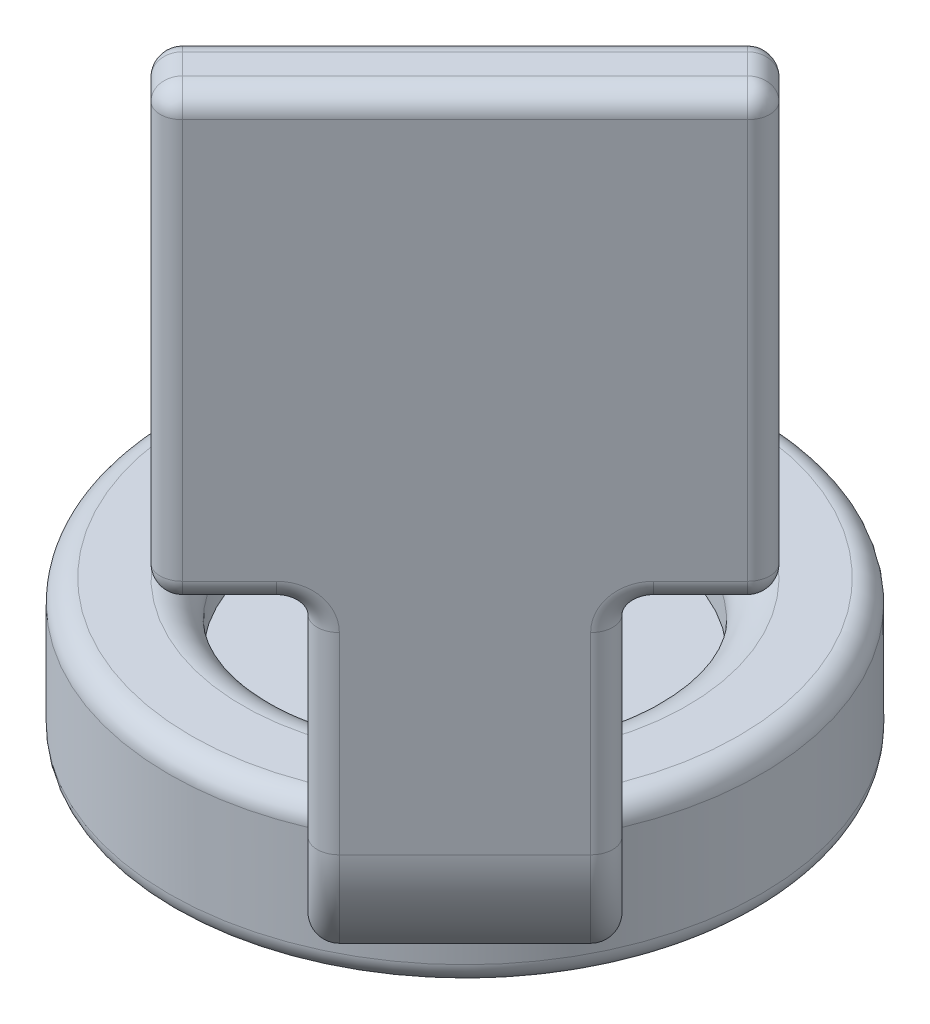
SolidWorks part; units mm, degrees
ref_plane "前视基准面" through (0, 0, 0) normal (0, 0, 1) x (1, 0, 0)
ref_plane "上视基准面" through (0, 0, 0) normal (0, 1, 0) x (1, 0, 0)
ref_plane "右视基准面" through (0, 0, 0) normal (1, 0, 0) x (0, 0, -1)
other "Configuration Table"
sketch "草图2" plane through (0, 0, 0) normal (0, 0, 1) x (1, 0, 0)
  line L1 (30, -3) -> (30, -6)
  line L2 (30, -6) -> (40, -6)
  line L3 (40, -6) -> (40, 5)
  line L4 (25, 5) -> (0, 5)
  line L5 (0, 5) -> (0, 0)
  line L6 (0, 0) -> (25, 0)
  line L7 (25, 0) -> (25, -3)
  line L8 (25, -3) -> (30, -3)
  line L9 (40, 5) -> (40, 14)
  line L10 (40, 14) -> (25, 14)
  line L11 (25, 14) -> (25, 5)
revolve "旋转1" add sketch "草图2" angle 360 about L5
sketch "草图3" plane through (0, 0, 0) normal (0, -1, 0) x (1, 0, 0)
  circle A0 centre (12.5, 0) radius 1.6
  circle A1 centre (0, -12.5) radius 1.6
  circle A2 centre (-12.5, 0) radius 1.6
  circle A3 centre (0, 12.5) radius 1.6
  point P13 (0, 0)
  dimension "D1" = 4
extrude "切除-拉伸1" cut sketch "草图3" against normal blind 10
fillet "圆角3" radius 5 1 edges at (0, 14, 25)
sketch "草图5" plane through (0, 5, 0) normal (0, 1, 0) x (1, 0, 0)
  line L3 (0, 0) -> (6.25, -6.25)
ref_plane "基准面1" through (0, 0, 0) normal (-0.7071, 0, 0.7071) x (0.7071, 0, 0.7071)
sketch "草图6" plane through (0, 0, 0) normal (-0.7071, 0, 0.7071) x (0.7071, 0, 0.7071)
  line L0 (30, 14) -> (30, 4)
  line L1 (50, 53) -> (60, 53)
  line L3 (60, 53) -> (60, 24)
  line L8 (50, 24) -> (50, 53)
  line L13 (40, 14) -> (30, 14)
  line L17 (50, 53) -> (60, 53)
  line L19 (40, 4) -> (30, 4)
  arc A0 (50, 24) -> (40, 14) centre (40, 24) cw
  arc A3 (40, 4) -> (60, 24) centre (40, 24) ccw
  dimension "D1" = 10
  dimension "D4" = 10
  dimension "D5" = 29
ref_plane "基准面2" through (0, 0, 0) normal (-0.7071, 0, 0.7071) x (0.7071, 0, 0.7071)
extrude "凸台-拉伸2" add sketch "草图6" along normal mid plane 30 contours L3 A3 L19 L0 L13 A0 L8 L17
fillet "圆角4" radius 0.5 4 edges at (-12.5, 5, -1.6) (12.5, 5, -1.6) (0, 5, -14.1) (0, 5, 10.9)
fillet "圆角11" radius 3 1 edges at (0, -6, 40)
sketch "草图7" plane through (0, 0, 0) normal (-0.7071, 0, 0.7071) x (0.7071, 0, 0.7071)
  line L1 (60, 113) -> (50, 113)
  line L2 (50, 113) -> (50, 53)
  line L3 (50, 53) -> (60, 53)
  line L4 (60, 53) -> (60, 113)
extrude "凸台-拉伸3" add sketch "草图7" along normal mid plane 60
fillet "圆角13" radius 1 2 edges at (0, -6, 30) (0, -3, 25)
fillet "圆角19" radius 3 29 edges at (37.8588, 4, 16.6456) (16.6456, 4, 37.8588) (37.8588, 14, 16.6456) (16.6456, 14, 37.8588) (28.2843, 53, 49.4975) (26.5165, 53, 58.3363) (19.4454, 53, 51.2652) (17.6777, 53, 60.1041) (14.1421, 83, 56.5685) (21.2132, 83, 63.6396) (17.6777, 113, 60.1041) (35.3553, 113, 35.3553) (42.4264, 113, 42.4264) (60.1041, 113, 17.6777) (56.5685, 83, 14.1421) (63.6396, 83, 21.2132) (60.1041, 53, 17.6777) (51.2652, 53, 19.4454) (58.3363, 53, 26.5165) (49.4975, 53, 28.2843) (24.7487, 38.5, 45.9619) (31.8198, 38.5, 53.033) (45.9619, 38.5, 24.7487) (53.033, 38.5, 31.8198) (48.8909, 9.8579, 27.6777) (27.6777, 9.8579, 48.8909) (43.8909, 16.9289, 22.6777) (22.6777, 16.9289, 43.8909) (-28.2843, 14, -28.2843)
